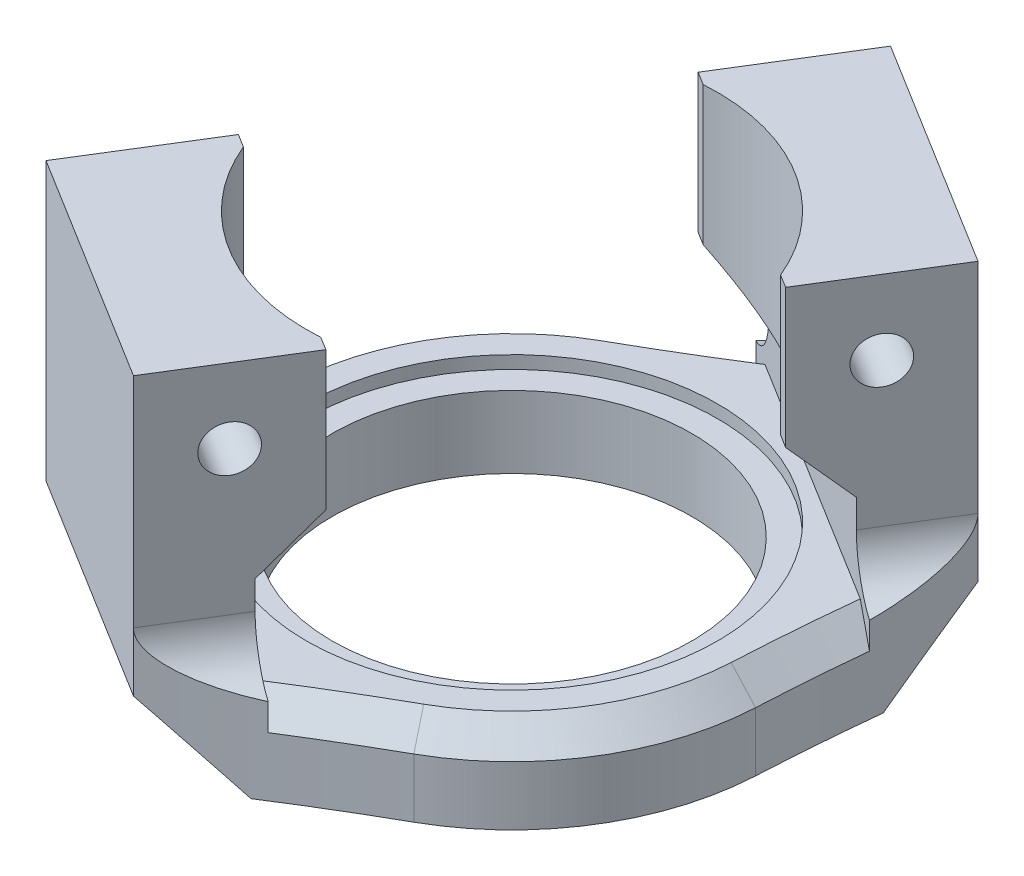
SolidWorks part; units mm, degrees
ref_plane "前视基准面" through (0, 0, 0) normal (0, 0, 1) x (1, 0, 0)
ref_plane "上视基准面" through (0, 0, 0) normal (0, 1, 0) x (1, 0, 0)
ref_plane "右视基准面" through (0, 0, 0) normal (1, 0, 0) x (0, 0, -1)
other "Configuration Table"
sketch "草图1" plane through (0, 0, 0) normal (0, 1, 0) x (1, 0, 0)
  circle A0 centre (0, 0) radius 7
  circle A1 centre (0, 0) radius 10
  dimension "D1" = 14
  dimension "D2" = 20
extrude "凸台-拉伸1" add sketch "草图1" along normal blind 2.8
sketch "草图2" plane through (0, 2.8, 0) normal (0, 1, 0) x (1, 0, 0)
  circle A1 centre (0, 0) radius 10 construction
  circle A2 centre (0, 0) radius 8
  circle A3 centre (0, 0) radius 10
  dimension "D1" = 16
extrude "凸台-拉伸2" add sketch "草图2" along normal blind 0.5
sketch "草图3" plane through (0, 0, 0) normal (0, -1, 0) x (1, 0, 0)
  line L0 (-8.9553, 4.45) -> (0, 10)
  line L1 (0, -10) -> (8.9553, -4.45)
  line L2 (0, -10) -> (0, 0) construction
  line L4 (0, 0) -> (7, 0) construction
  circle A0 centre (0, 0) radius 10 construction
  circle A1 centre (0, 0) radius 7 construction
  circle A2 centre (0, 0) radius 10
  circle A3 centre (0, 0) radius 10
  circle M4 centre (0, 0) radius 10
  dimension "D1" = 17
  dimension "D2" = 0
extrude "凸台-拉伸3" add sketch "草图3" against normal blind 8.4 contours L0 M4 | L1 M4
sketch "草图5" plane through (0, 8.4, 0) normal (0, 1, 0) x (1, 0, 0)
  line L0 (0, -10) -> (-1.8117, -12.9233)
  line L9 (1.8117, 12.9233) -> (10.767, 7.3733)
  line L10 (10.767, 7.3733) -> (7.9017, 2.75)
  line L11 (7.9017, 2.75) -> (-1.0536, 8.3)
  line L12 (-1.0536, 8.3) -> (1.8117, 12.9233)
  line L13 (-7.9017, -2.75) -> (1.0536, -8.3)
  line L14 (1.0536, -8.3) -> (-1.8117, -12.9233)
  line L15 (-1.8117, -12.9233) -> (-10.767, -7.3733)
  line L16 (-10.767, -7.3733) -> (-7.9017, -2.75)
  arc A0 (7.3882, 3.0682) -> (-0.54, 7.9818) centre (0, 0) ccw construction
  arc A1 (-7.3882, -3.0682) -> (0.54, -7.9818) centre (0, 0) ccw construction
  line M1 (0, 10) -> (8.9553, 4.45)
  arc M2 (8.9553, 4.45) -> (0, 10) centre (0, 0) ccw
  dimension "D1" = 8
  dimension "D3" = 10.5357
extrude "凸台-拉伸4" add sketch "草图5" along normal blind 5.4 contours A1 L13 L16 L15 L0 L14 | L12 L10 L9 M2 | A0 L11 L10 L12 M1 | M2 M1
sketch "草图7" plane through (-4.4777, 0, -2.775) normal (-0.85, 0, -0.5268) x (-0.5268, 0, 0.85)
  circle A2 centre (9.2196, 10.9) radius 0.9
  circle A3 centre (-9.2196, 10.9) radius 0.9
extrude "切除-拉伸1" cut sketch "草图7" against normal through all
chamfer "倒角2" distance 2 angle 45 2 edges at (-4.4777, 8.4, 7.225) (4.4777, 8.4, -7.225)
sketch "草图8" plane through (0, 0, 0) normal (0, -1, 0) x (1, 0, 0)
  line L0 (10.767, -7.3733) -> (8.9553, -4.45) construction
  line L1 (0, -10) -> (1.8117, -12.9233) construction
  line L2 (1.8117, -12.9233) -> (10.767, -7.3733) construction
  line L3 (-10.767, 7.3733) -> (-8.9553, 4.45) construction
  line L4 (0, 10) -> (-1.8117, 12.9233) construction
  line L5 (-1.8117, 12.9233) -> (-10.767, 7.3733) construction
  line L6 (10.767, -7.3733) -> (8.9553, -4.45)
  line L7 (0, -10) -> (1.8117, -12.9233)
  line L8 (1.8117, -12.9233) -> (10.767, -7.3733)
  line L9 (-10.767, 7.3733) -> (-8.9553, 4.45)
  line L10 (0, 10) -> (-1.8117, 12.9233)
  line L11 (-1.8117, 12.9233) -> (-10.767, 7.3733)
  arc A0 (0, -10) -> (8.9553, -4.45) centre (0, 0) ccw construction
  arc A1 (0, 10) -> (-8.9553, 4.45) centre (0, 0) ccw construction
  arc A2 (0, -10) -> (8.9553, -4.45) centre (0, 0) ccw
  arc A3 (0, 10) -> (-8.9553, 4.45) centre (0, 0) ccw
extrude "凸台-拉伸5" add sketch "草图8" against normal up to next
fillet "圆角2" radius 82.5 8 edges at (0, 1.65, -10) (8.9553, 1.65, -4.45) (9.8612, 0, -5.9117) (0.9059, 0, -11.4617) (0, 1.65, 10) (-8.9553, 1.65, 4.45) (-9.8612, 0, 5.9117) (-0.9059, 0, 11.4617)
chamfer "倒角4" distance 3 angle 45 2 edges at (6.2894, 0, -10.1483) (-6.2894, 0, 10.1483)
fillet "圆角3" radius 2 4 edges at (0.9059, 3.3, -11.4617) (-9.8612, 3.3, 5.9117) (-0.9059, 3.3, 11.4617) (9.8612, 3.3, -5.9117)
sketch "草图9" plane through (0, 13.8, 0) normal (0, 1, 0) x (1, 0, 0)
  line L0 (-3.4241, -5.525) -> (3.4241, 5.525) construction
  line L1 (-7.9017, -2.75) -> (1.0536, -8.3) construction
  line L2 (7.9017, 2.75) -> (-1.0536, 8.3) construction
  circle A1 centre (0, 0) radius 8
  dimension "D1" = 16
extrude "切除-拉伸2" cut sketch "草图9" against normal blind 7
chamfer "倒角5" distance 1 angle 45 6 edges at (-3.1079, 3.3, -9.7537) (-10.1177, 3.3, 1.5572) (-8.5, 3.3, -5.2678) (3.1079, 3.3, 9.7537) (10.1177, 3.3, -1.5572) (8.5, 3.3, 5.2678)
